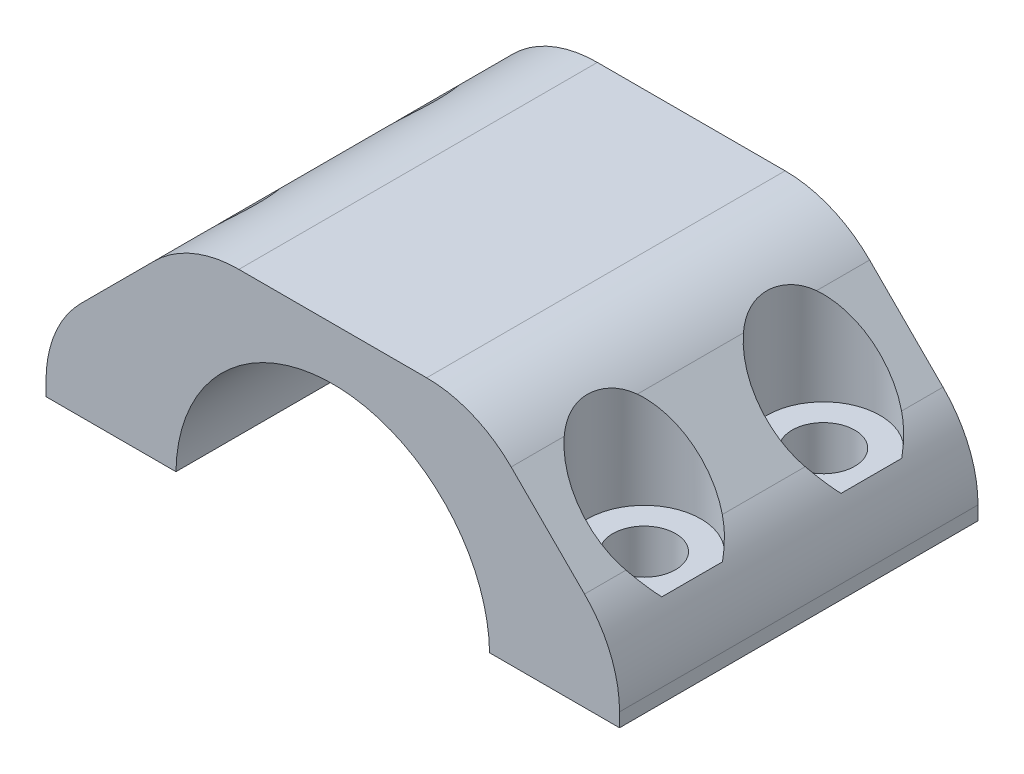
SolidWorks part; units mm, degrees
ref_plane "Front Plane" through (0, 0, 0) normal (0, 0, 1) x (1, 0, 0)
ref_plane "Top Plane" through (0, 0, 0) normal (0, 1, 0) x (1, 0, 0)
ref_plane "Right Plane" through (0, 0, 0) normal (1, 0, 0) x (0, 0, -1)
sketch "Sketch1" plane through (0, 0, 0) normal (0, 0, 1) x (1, 0, 0)
  line L1 (-24, -8.75) -> (24, -8.75)
  line L2 (-24, -8.75) -> (-24, 8.75)
  line L3 (-24, 8.75) -> (24, 8.75)
  line L4 (24, -8.75) -> (24, 8.75)
  line L5 (-24, -8.75) -> (24, 8.75) construction
  line L6 (-24, 8.75) -> (24, -8.75) construction
  point P0 (0, 0)
  dimension "D1" = 48
  dimension "D2" = 17.5
extrude "body" add sketch "Sketch1" along normal blind 30
sketch "Sketch2" plane through (0, 0, 0) normal (0, 0, 1) x (1, 0, 0)
  line L0 (0, -8.75) -> (0, 13.732) construction
  line L1 (-24, -8.75) -> (24, -8.75) construction
  line L2 (13.125, -8.75) -> (-13.125, -8.75)
  arc A0 (13.125, -8.75) -> (-13.125, -8.75) centre (0, -8.75) ccw
  dimension "D1" = 26.25
extrude "tube_cutout" cut sketch "Sketch2" along normal through all
sketch "Sketch3" plane through (0, -8.75, 0) normal (0, -1, 0) x (1, 0, 0)
  line L0 (18.5625, 30) -> (18.5625, 0) construction
  line L1 (13.125, 30) -> (24, 30) construction
  line L2 (13.125, 0) -> (24, 0) construction
  line L3 (0, 0) -> (0, 25.8019) construction
  circle A0 centre (18.5625, 22.5) radius 2.625
  circle A1 centre (18.5625, 7.5) radius 2.625
  circle A2 centre (-18.5625, 7.5) radius 2.625
  circle A3 centre (-18.5625, 22.5) radius 2.625
  dimension "D1" = 5.25
  dimension "D2" = 7.5
  dimension "D3" = 22.5
extrude "M5" cut sketch "Sketch3" against normal through all
sketch "Sketch4" plane through (0, 0, 0) normal (0, 0, 1) x (1, 0, 0)
  line L0 (-24, 8.75) -> (-24, -3.25)
  line L1 (-24, 8.75) -> (-24, -8.75) construction
  line L2 (-24, -3.25) -> (-12, 8.75)
  line L3 (24, 8.75) -> (-24, 8.75) construction
  line L4 (-12, 8.75) -> (-24, 8.75)
  line L5 (0, 0) -> (0, 12.9873) construction
  line L6 (-24, -8.75) -> (-13.125, -8.75) construction
  line L7 (24, -3.25) -> (12, 8.75)
  line L8 (24, 8.75) -> (24, -3.25)
  line L9 (12, 8.75) -> (24, 8.75)
  dimension "D1" = 12
  dimension "D2" = 5.5
extrude "slope" cut sketch "Sketch4" along normal through all
sketch "Sketch5" plane through (0, -8.75, 0) normal (0, -1, 0) x (1, 0, 0)
  line L0 (0, 0) -> (0, 28.2785) construction
  circle A7 centre (18.5625, 22.5) radius 4.75
  circle A8 centre (18.5625, 7.5) radius 4.75
  circle A9 centre (-18.5625, 7.5) radius 4.75
  circle A10 centre (-18.5625, 22.5) radius 4.75
  dimension "D1" = 9.5
extrude "bolt_head_cutout" cut sketch "Sketch5" against normal blind 23 from offset 6.5 offset against normal yes
fillet "fillet" radius 10 4 edges at (24, -3.25, 15) (12, 8.75, 15) (-24, -3.25, 15) (-12, 8.75, 15)
sketch "Sketch7" plane through (0, -8.75, 0) normal (0, -1, 0) x (1, 0, 0)
  line L1 (24, 0) -> (-24, 0)
  line L2 (24, 0) -> (24, 30)
  line L3 (24, 30) -> (-24, 30)
  line L4 (-24, 0) -> (-24, 30)
extrude "clearance" cut sketch "Sketch7" against normal blind 0.2
